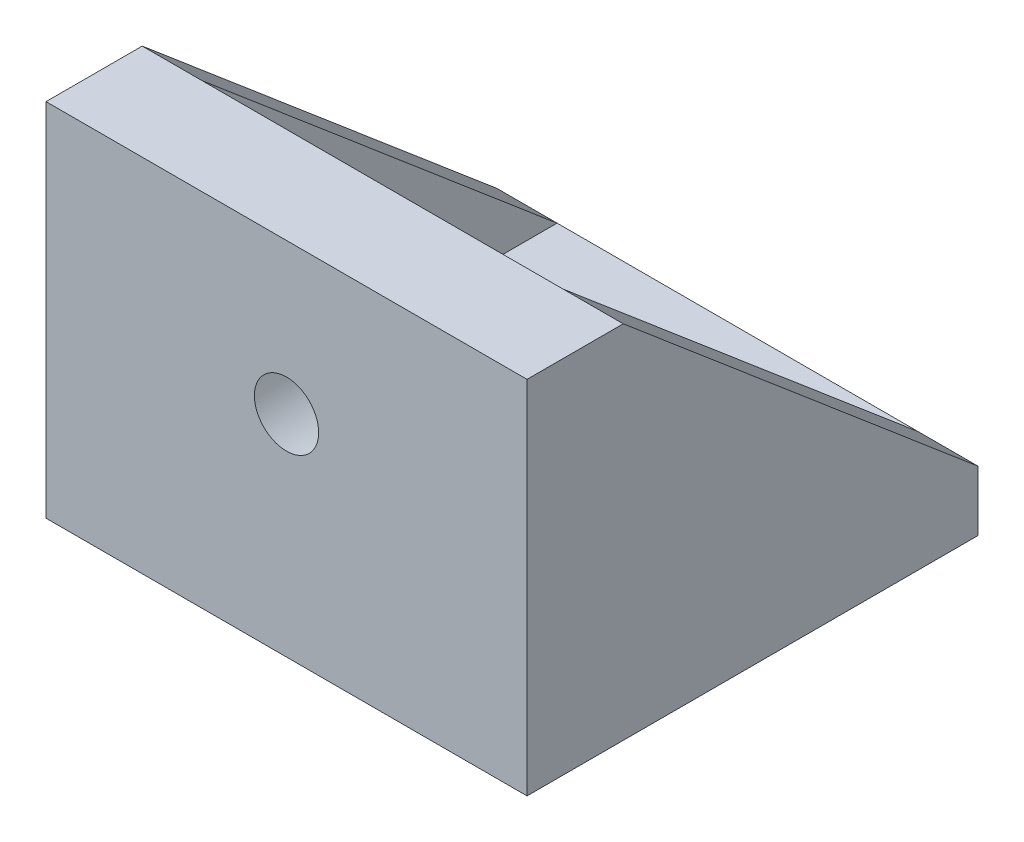
SolidWorks part; units mm, degrees
ref_plane "Front Plane" through (0, 0, 0) normal (0, 0, 1) x (1, 0, 0)
ref_plane "Top Plane" through (0, 0, 0) normal (0, 1, 0) x (1, 0, 0)
ref_plane "Right Plane" through (0, 0, 0) normal (1, 0, 0) x (0, 0, -1)
sketch "Sketch1" plane through (0, 0, 0) normal (0, 1, 0) x (1, 0, 0)
  line L1 (-20, 18.75) -> (20, 18.75)
  line L2 (-20, 18.75) -> (-20, -18.75)
  line L3 (-20, -18.75) -> (20, -18.75)
  line L4 (20, 18.75) -> (20, -18.75)
  line L5 (-20, 18.75) -> (20, -18.75) construction
  line L6 (-20, -18.75) -> (20, 18.75) construction
  point P0 (0, 0)
  dimension "D1" = 37.5
  dimension "D2" = 40
extrude "Boss-Extrude1" add sketch "Sketch1" along normal blind 5
sketch "Sketch2" plane through (0, 0, 18.75) normal (0, 0, 1) x (1, 0, 0)
  line L14 (-20, 5) -> (20, 5) construction
  line L16 (0, 0) -> (0, 30) construction
  line L17 (20, 0) -> (-20, 0)
  line L18 (20, 0) -> (20, 30)
  line L19 (20, 30) -> (-20, 30)
  line L20 (-20, 0) -> (-20, 30)
  line L21 (20, 0) -> (-20, 30) construction
  line L22 (20, 30) -> (-20, 0) construction
  point P4 (0, 15)
  point P11 (0, 15)
  dimension "D1" = 25
extrude "Boss-Extrude2" add sketch "Sketch2" against normal blind 8
sketch "Sketch3" plane through (20, 0, 0) normal (1, 0, 0) x (0, 0, -1)
  line L0 (-10.75, 30) -> (18.75, 5)
  line L1 (18.75, 5) -> (-10.75, 5)
  line L2 (-10.75, 5) -> (-10.75, 30)
extrude "Boss-Extrude3" add sketch "Sketch3" against normal blind 5
extrude "Boss-Extrude4" add sketch "Sketch3<2>" along normal blind 5 from surface starting at face at (-20, 11.6667, 3.5833)
sketch "Sketch3<2>" plane through (20, 0, 0) normal (1, 0, 0) x (0, 0, -1) same geometry as "Sketch3"
sketch "Sketch4" plane through (0, 5, 0) normal (0, 1, 0) x (1, 0, 0)
  line L0 (0, 11.5) -> (0, 1.5) construction
  line L1 (0, 1.5) -> (8.6603, -3.5) construction
  line L2 (0, 1.5) -> (-8.6603, -3.5) construction
  line L3 (0, -10.75) -> (0, 18.75) construction
  line L4 (15, -10.75) -> (-15, -10.75) construction
  line L5 (15, 18.75) -> (-15, 18.75) construction
  line L7 (-8.6603, -3.5) -> (-8.6603, -10.75) construction
  line L8 (15, -10.75) -> (-15, -10.75) construction
  line L10 (0, 11.5) -> (0, 18.75) construction
  point P6 (0, 11.5)
  point P7 (-8.6603, -3.5)
  point P8 (8.6603, -3.5)
  dimension "D1" = 120
  dimension "D2" = 120
  dimension "D3" = 10
hole_wizard "CSK for M3 Flat Head Machine Screw1" positions "Sketch4" profile "Sketch5" countersink size "M3" standard "ANSI Metric"
sketch "Sketch5" plane through (8.6603, 5, 3.5) normal (1, 0, 0) x (0, 0, 1)
  line L0 (0, 0) -> (0, 7.0215)
  line L1 (0, 7.0215) -> (1.7, 6)
  line L2 (1.7, 6) -> (1.7, 1.45)
  line L3 (1.7, 1.45) -> (3.15, 0)
  line L5 (3.15, 0) -> (0, 0)
  line L6 (-1.7, 1.45) -> (-3.15, 0) construction
  line L10 (0, 7.0215) -> (-1.7, 6) construction
  line L11 (0, -6.35) -> (0, 107.95) construction
  dimension "Hole Dia." = 3.4
  dimension "Hole Depth" = 6
  dimension "Near C'Sink Dia." = 6.3
  dimension "Near C'Sink Angle" = 90
  dimension "Drill Angle" = 118
sketch "Sketch6" plane through (0, 0, 10.75) normal (0, 0, -1) x (-1, 0, 0)
  line L0 (-15, 5) -> (15, 30)
  point P4 (0, 17.5)
hole_wizard "Ø12.0 (12) Diameter Hole1" positions "Sketch6" profile "Sketch8" hole size "Ø12.0" standard "ANSI Metric"
sketch "Sketch8" plane through (0, 17.5, 10.75) normal (1, 0, 0) x (0, 1, 0)
  line L0 (0, 0) -> (0, 9.6052)
  line L1 (0, 9.6052) -> (6, 6)
  line L2 (6, 6) -> (6, 0)
  line L5 (6, 0) -> (0, 0)
  line L10 (0, 9.6052) -> (-6, 6) construction
  line L11 (0, -6.35) -> (0, 107.95) construction
  dimension "Hole Dia." = 12
  dimension "Hole Depth" = 6
  dimension "Drill Angle" = 118
